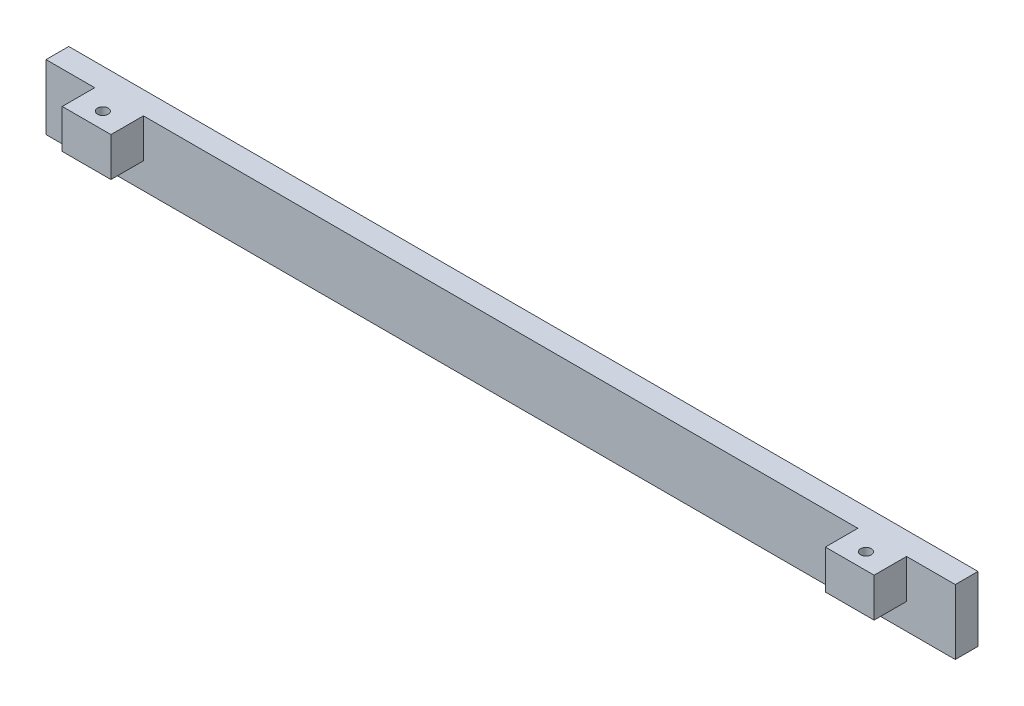
SolidWorks part; units mm, degrees
material "6061 合金"
ref_plane "前视基准面" through (0, 0, 0) normal (0, 0, 1) x (1, 0, 0)
ref_plane "上视基准面" through (0, 0, 0) normal (0, 1, 0) x (1, 0, 0)
ref_plane "右视基准面" through (0, 0, 0) normal (1, 0, 0) x (0, 0, -1)
other "斜边"
sketch "草图1" plane through (0, 0, 0) normal (1, 0, 0) x (0, 0, -1)
  line L1 (-3.5, -10) -> (3.5, -10)
  line L2 (-3.5, -10) -> (-3.5, 10)
  line L3 (-3.5, 10) -> (3.5, 10)
  line L4 (3.5, -10) -> (3.5, 10)
  line L5 (-3.5, -10) -> (3.5, 10) construction
  line L6 (-3.5, 10) -> (3.5, -10) construction
  point P0 (0, 0)
  dimension "D1" = 7
  dimension "D2" = 20
extrude "凸台-拉伸1" add sketch "草图1" along normal mid plane 280
sketch "草图2" plane through (0, 0, 3.5) normal (0, 0, 1) x (1, 0, 0)
  line L0 (0, 0) -> (0, 57.0616) construction
  line L1 (-125, 10) -> (-110, 10)
  line L2 (-125, 10) -> (-125, -2)
  line L3 (-125, -2) -> (-110, -2)
  line L4 (-110, 10) -> (-110, -2)
  line L5 (140, -10) -> (-140, -10) construction
  line L6 (140, 10) -> (-140, 10) construction
  dimension "D1" = 8
  dimension "D2" = 15
  dimension "D3" = 250
extrude "凸台-拉伸2" add sketch "草图2" along normal blind 10
mirror "镜向1" about plane through (0, 0, 0) normal (1, 0, 0) of "凸台-拉伸2"
hole_wizard "M4 螺纹孔1" positions "草图4" profile "草图3" tap size "M4" standard "GB" end condition up to next
sketch "草图4" plane through (0, -2, 0) normal (0, -1, 0) x (-1, 0, 0)
  line L0 (0, 0) -> (0, -40.588) construction
  line L1 (-110, -13.5) -> (-110, -3.5) construction
  line L2 (-117.5, -8.5) -> (-110, -8.5) construction
  point P0 (-117.5, -8.5)
  point P9 (117.5, -8.5)
  dimension "D1" = 235
  dimension "D2" = 7.5
sketch "草图3" plane through (117.5, -2, 8.5) normal (1, 0, 0) x (0, 0, -1)
  line L0 (0, 0) -> (0, 12)
  line L1 (0, 12) -> (1.65, 12)
  line L2 (1.65, 12) -> (1.65, 0)
  line L5 (1.65, 0) -> (0, 0)
  line L11 (0, -6.35) -> (0, 107.95) construction
  dimension "通孔螺纹孔钻头直径" = 3.3
  dimension "通孔螺纹孔钻头深度" = 12
cosmetic thread "孔螺蚊线1" parameters "D2"=4
cosmetic thread "孔螺蚊线2" parameters "D2"=4
sketch "草图5" [suppressed] plane through (0, 0, -3.5) normal (0, 0, -1) x (-1, 0, 0)
  line L0 (0, 0) -> (0, 56.8035) construction
  line L1 (-42, 10) -> (-30, -2)
  line L2 (-145, 10) -> (145, 10) construction
  line L3 (42, 10) -> (30, -2)
  line L4 (-30, -2) -> (30, -2)
  line L5 (-145, -10) -> (145, -10) construction
  dimension "D1" = 8
  dimension "D2" = 45
  dimension "D3" = 84
extrude "切除-拉伸1" [suppressed] cut sketch "草图5" against normal through all and the other way through all flip side to cut
